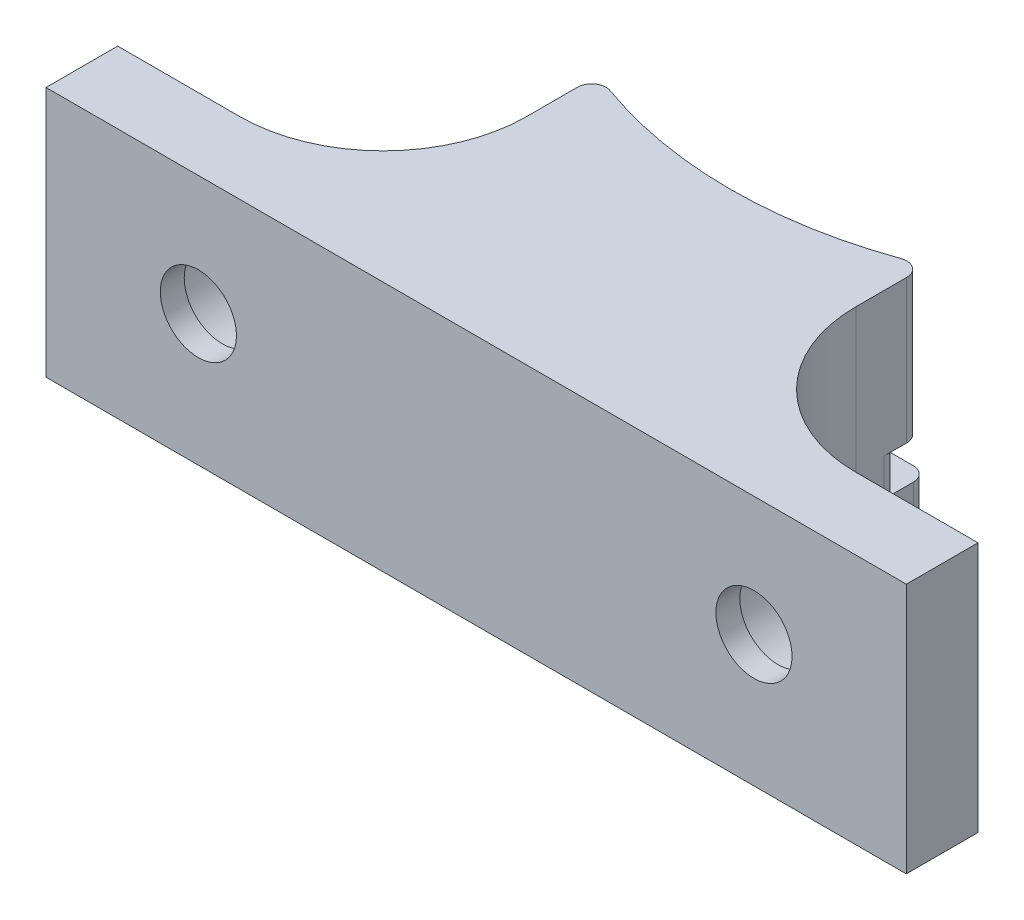
SolidWorks part; units mm, degrees
other "Markup1"
sketch "Sketch4" plane through (-125.7365, 25.4, -65.9837) normal (-0.2855, 0.1861, -0.9401) x (-0.9569, -0.1093, 0.269)
ref_plane "Front Plane" through (0, 0, 0) normal (0, 0, 1) x (1, 0, 0)
ref_plane "Top Plane" through (0, 0, 0) normal (0, 1, 0) x (1, 0, 0)
ref_plane "Right Plane" through (0, 0, 0) normal (1, 0, 0) x (0, 0, -1)
sketch "Sketch1" plane through (0, 0, 0) normal (0, 1, 0) x (1, 0, 0)
  line L0 (29.1702, 25.4) -> (0, 95.8231) construction
  line L1 (76.2, 25.4) -> (-76.2, 25.4)
  line L2 (76.2, 25.4) -> (76.2, -25.4)
  line L3 (76.2, -25.4) -> (-76.2, -25.4)
  line L4 (-76.2, 25.4) -> (-76.2, -25.4)
  line L5 (76.2, 25.4) -> (-76.2, -25.4) construction
  line L6 (76.2, -25.4) -> (-76.2, 25.4) construction
  line L7 (0, 95.8231) -> (-29.1702, 25.4) construction
  arc A0 (-29.1702, 25.4) -> (29.1702, 25.4) centre (0, 95.8231) ccw
  point P0 (0, 0)
  point P9 (-39.4506, 66.5343)
  dimension "D1" = 76.2254
  dimension "D2" = 45
  dimension "D3" = 152.4
  dimension "D4" = 50.8
extrude "Boss-Extrude1" add sketch "Sketch1" along normal blind 25.4 contours A0 L1 L4 L3 L2 region at (0, 0, 0.6983)
sketch "Sketch2" plane through (0, 0, 0) normal (0, -1, 0) x (1, 0, 0)
  line L1 (-76.2, 25.4) -> (76.2, 25.4)
  line L6 (-76.2, 25.4) -> (-76.2, -21.59)
  line L7 (-76.2, -25.4) -> (-76.2, 25.4) construction
  line L8 (-76.2, -21.59) -> (-29.8504, -21.59)
  line L9 (76.2, 25.4) -> (76.2, -21.59)
  line L10 (76.2, -21.59) -> (29.8504, -21.59)
  line L11 (-29.1702, -25.4) -> (-76.2, -25.4) construction
  arc A1 (-29.8504, -21.59) -> (29.8504, -21.59) centre (0, -95.8231) cw
  arc A3 (29.1702, -25.4) -> (-29.1702, -25.4) centre (0, -95.8231) ccw construction
  point P1 (101.4379, -47.8718)
  point P8 (0, 0)
  point P17 (-90.7346, -39.8237)
  point P18 (0, 0)
  point P19 (0, 0)
  point P20 (0, 0)
  dimension "D1" = 80.01
  dimension "D2" = 3.81
extrude "Boss-Extrude2" add sketch "Sketch2" along normal blind 6.604
sketch "Sketch3" plane through (0, -6.604, 0) normal (0, -1, 0) x (1, 0, 0)
  line L0 (76.2, -21.59) -> (76.2, 25.4) construction
  line L1 (-76.2, 25.4) -> (76.2, 25.4)
  line L2 (-76.2, 25.4) -> (-76.2, -25.4)
  line L3 (-76.2, -25.4) -> (76.2, -25.4)
  line L4 (76.2, 25.4) -> (76.2, -25.4)
  line L5 (76.2, -25.4) -> (29.1702, -25.4) construction
  point P12 (0, 0)
  point P14 (0, -88.8832)
  point P15 (0, -87.8806)
extrude "Boss-Extrude3" add sketch "Sketch3" along normal blind 12.446
sketch "Sketch5" plane through (0, 25.4, 0) normal (0, 1, 0) x (1, 0, 0)
  line L0 (-29.1702, 25.4) -> (-29.1702, -12.7)
  line L1 (-29.1702, -12.7) -> (-76.2, -12.7)
  line L2 (-76.2, 25.4) -> (-76.2, -25.4) construction
  line L3 (-76.2, -12.7) -> (-76.2, 25.4)
  line L4 (-76.2, 25.4) -> (76.2, 25.4)
  line L5 (76.2, 25.4) -> (76.2, -12.7)
  line L6 (76.2, -12.7) -> (29.1702, -12.7)
  line L7 (29.1702, -12.7) -> (29.1702, 25.4)
  line L8 (76.2, 25.4) -> (76.2, -25.4) construction
  line L9 (-29.1702, 25.4) -> (-76.2, 25.4) construction
  line L10 (76.2, -25.4) -> (-76.2, -25.4) construction
  arc A0 (-29.1702, 25.4) -> (29.1702, 25.4) centre (0, 95.8231) ccw
  arc A3 (-29.1702, 25.4) -> (29.1702, 25.4) centre (0, 95.8231) ccw construction
  point P18 (-53.9127, 15.379)
  point P21 (0, 0)
  point P22 (-48.521, 8.3711)
  point P23 (-37.2377, 8.0131)
  line M8 (-29.1702, 25.4) -> (-76.2, 25.4)
  line M9 (-76.2, 25.4) -> (-76.2, -25.4)
  line M11 (76.2, -25.4) -> (76.2, 25.4)
  line M12 (76.2, 25.4) -> (29.1702, 25.4)
  dimension "D1" = 12.7
extrude "Cut-Extrude1" cut sketch "Sketch5" against normal through all contours L1 L0 M8 M9 | L7 L6 M11 M12 region at (-52.6851, 25.4, -6.35) region at (52.6851, 25.4, -6.35)
fillet "Fillet1" radius 2.54 6 edges at (29.1702, -12.827, -25.4) (-29.1702, -12.827, -25.4) (-29.1702, -3.302, -21.3201) (29.1702, -3.302, -21.3201) (29.1702, 12.7, -25.4) (-29.1702, 12.7, -25.4)
fillet "Fillet2" radius 25.4 2 edges at (29.1702, 3.175, 12.7) (-29.1702, 3.175, 12.7)
sketch "Sketch6" plane through (0, 0, 0) normal (0, 0, 1) x (1, 0, 0)
  line L0 (49.2125, 4.191) -> (-49.2125, 4.191) construction
  line L1 (29.1702, -19.05) -> (54.5702, -19.05) construction
  circle A0 centre (49.2125, 4.191) radius 9.9187
  circle A1 centre (-49.2125, 4.191) radius 9.9187
  point P4 (0, 4.191)
  dimension "D1" = 98.425
  dimension "D3" = 19.8374
  dimension "D2" = 23.241
extrude "Cut-Extrude2" cut sketch "Sketch6" along normal offset from surface 4.2418 and the other way through all from surface up to face at (0, 3.175, 25.4) starting at face at (65.3851, 3.175, 12.7)
sketch "Sketch7" plane through (0, 0, 21.1582) normal (0, 0, -1) x (-1, 0, 0)
  circle A0 centre (-49.2125, 4.191) radius 6.7437
  circle A1 centre (49.2125, 4.191) radius 6.7437
  arc A2 (-54.5702, -4.1562) -> (-54.5702, 12.5382) centre (-49.2125, 4.191) ccw construction
  circle A3 centre (49.2125, 4.191) radius 9.9187 construction
  dimension "D1" = 13.4874
extrude "Cut-Extrude3" cut sketch "Sketch7" against normal through all
